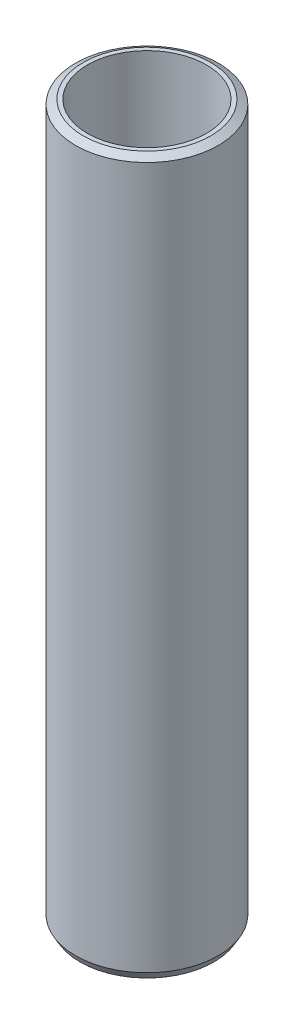
SolidWorks part; units mm, degrees
ref_plane "Front Plane" through (0, 0, 0) normal (0, 0, 1) x (1, 0, 0)
ref_plane "Top Plane" through (0, 0, 0) normal (0, 1, 0) x (1, 0, 0)
ref_plane "Right Plane" through (0, 0, 0) normal (1, 0, 0) x (0, 0, -1)
sketch "Sketch1" plane through (0, 0, 0) normal (0, 1, 0) x (1, 0, 0)
  circle A0 centre (0, 0) radius 60
  dimension "SHAFT_OD" = 120
extrude "Boss-Extrude1" add sketch "Sketch1" along normal blind 600
sketch "Sketch2" plane through (0, 0, 0) normal (0, 1, 0) x (1, 0, 0)
  circle A0 centre (0, 0) radius 49.9956
  dimension "BORE_D" = 99.9912
extrude "Cut-Extrude1" cut sketch "Sketch2" along normal through all
chamfer "Chamfer1" distance 3.733 angle 60 2 edges at (0, 600, 60) (0, 0, 60) first distance on face at (0, 600, 60) first distance on face at (0, 0, 49.9956)
